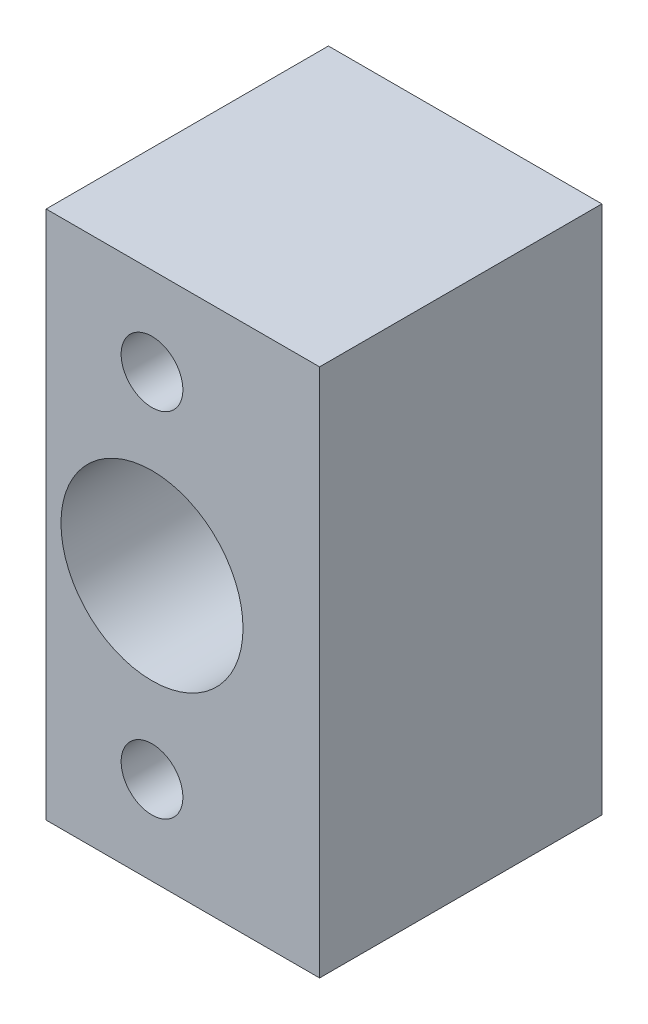
SolidWorks part; units mm, degrees
material "6061-T4 (SS)"
ref_plane "Front Plane" through (0, 0, 0) normal (0, 0, 1) x (1, 0, 0)
ref_plane "Top Plane" through (0, 0, 0) normal (0, 1, 0) x (1, 0, 0)
ref_plane "Right Plane" through (0, 0, 0) normal (1, 0, 0) x (0, 0, -1)
sketch "Sketch1" plane through (0, 0, 0) normal (0, 0, 1) x (1, 0, 0)
  line L5 (-6, 6) -> (0, 0) construction
  line L6 (0, 0) -> (6, 6) construction
  line L7 (9.5, 15) -> (-9.5, 15)
  line L8 (9.5, 15) -> (9.5, -15)
  line L9 (9.5, -15) -> (-9.5, -15)
  line L10 (-9.5, 15) -> (-9.5, -15)
  line L11 (9.5, 15) -> (-9.5, -15) construction
  line L12 (9.5, -15) -> (-9.5, 15) construction
  point P0 (0, 0)
  dimension "D1" = 19
  dimension "D4" = 30
extrude "Boss-Extrude1" add sketch "Sketch1" along normal blind 18
sketch "Sketch2" plane through (0, 0, 18) normal (0, 0, 1) x (1, 0, 0)
  circle A0 centre (0, 0) radius 5.1594
  dimension "D1" = 10.3187
extrude "Cut-Extrude1" cut sketch "Sketch2" against normal blind 11.5 contours A0
sketch "Sketch4" plane through (0, 0, 6.5) normal (0, 0, 1) x (1, 0, 0)
  circle A0 centre (0, 0) radius 4.8
  dimension "D1" = 9.6
extrude "Cut-Extrude3" cut sketch "Sketch4" against normal blind 0.5
sketch "Sketch5" plane through (0, 0, 6) normal (0, 0, 1) x (1, 0, 0)
  circle A0 centre (0, 0) radius 2.3813
  dimension "D1" = 4.7625
extrude "Cut-Extrude4" cut sketch "Sketch5" against normal blind 8 and the other way through all
sketch "Sketch6" plane through (0, 0, 0) normal (0, 0, 1) x (1, 0, 0)
  line L0 (-6, 15) -> (-6, -15)
  line L3 (9.5, 15) -> (-9.5, 15) construction
  line L4 (-9.5, -15) -> (9.5, -15) construction
  circle A0 centre (0, 0) radius 5.1594 construction
  point P6 (-6, 0)
  dimension "D1" = 6
extrude "Cut-Extrude6" cut sketch "Sketch6" against normal through all and the other way through all flip side to cut
sketch "Sketch11" plane through (0, 0, 0) normal (0, 0, -1) x (-1, 0, 0)
  line L1 (6, 15) -> (-9.5, 15)
  line L2 (6, 15) -> (6, -15)
  line L3 (6, -15) -> (-9.5, -15)
  line L4 (-9.5, 15) -> (-9.5, -15)
extrude "Boss-Extrude5" add sketch "Sketch11" along normal blind 5
sketch "Sketch12" plane through (0, 0, -5) normal (0, 0, -1) x (-1, 0, 0)
  circle A0 centre (0, 0) radius 4
  dimension "D1" = 8
extrude "Cut-Extrude8" cut sketch "Sketch12" against normal blind 7.9
sketch "Sketch13" plane through (0, 0, -5) normal (0, 0, -1) x (-1, 0, 0)
  line L2 (6, 15) -> (-9.5, 15) construction
  line L3 (0, 15) -> (0, -15) construction
  line L4 (-9.5, -15) -> (6, -15) construction
  circle A1 centre (0, -10) radius 1.75
  circle A2 centre (0, 10) radius 1.75
  point P0 (0, 5)
  point P4 (0, -5)
  point P6 (0, 0)
  dimension "D3" = 3.5
  dimension "D4" = 10
  dimension "D1" = 5
  dimension "D2" = 5
extrude "Cut-Extrude9" cut sketch "Sketch13" against normal through all
sketch "Sketch15" plane through (0, -15, 0) normal (0, -1, 0) x (1, 0, 0)
  line L1 (-6, -5) -> (9.5, -5) construction
  line L2 (-6, -5) -> (-6, 16) construction
  line L3 (-6, 16) -> (9.5, 16)
  line L4 (9.5, -5) -> (9.5, 16) construction
  line L5 (9.5, 18) -> (9.5, -5) construction
  line L6 (-6, 16) -> (9.5, 16)
  line L7 (-6, 16) -> (-6, 17) construction
  line L8 (-6, 17) -> (9.5, 17) construction
  line L9 (9.5, 16) -> (9.5, 17) construction
  line L10 (-6, -5) -> (9.5, -5)
  line L11 (-6, 18) -> (9.5, 18)
  line L12 (-6, 18) -> (-6, 16)
  line L13 (-6, 16) -> (9.5, 16)
  line L14 (9.5, 18) -> (9.5, 16)
  line L15 (-6, -5) -> (-6, 0)
  line L16 (-6, 0) -> (9.5, 0)
  line L17 (9.5, -5) -> (9.5, 0)
  line M5 (9.5, 18) -> (-6, 18)
  line M6 (-6, 18) -> (-6, -5)
  line M8 (9.5, -5) -> (9.5, 18)
  dimension "D1" = 21
  dimension "D2" = 1
  dimension "D3" = 5
extrude "Cut-Extrude11" cut sketch "Sketch15" against normal blind 41 contours L3 M6 M8 M5 | L15 L10 L17 L16 region at (1.75, -15, 17)
ref_axis "Axis1" through (-6, -15, 0) along (0.4148, 0.8029, 0.4282)
ref_plane "Plane2" through (-6, -15, 0) normal (0.4148, 0.8029, 0.4282) x (0.9099, -0.366, -0.1952)
sketch "Sketch17" plane through (-6, -15, 0) normal (0.4148, 0.8029, 0.4282) x (0.9099, -0.366, -0.1952)
  circle A0 centre (0, 0) radius 5
  dimension "D1" = 10
extrude "Cut-Extrude12" cut sketch "Sketch17" along normal blind 2
sketch "Sketch18" plane through (-5.1983, -10.0612, -5.366) normal (-0.4148, -0.8029, -0.4282) x (0.9088, -0.3427, -0.2379)
  point P0 (-0.3126, 7.052)
sketch "Sketch20" plane through (0, 0, 0) normal (0, 0, -1) x (-1, 0, 0)
  circle A0 centre (0, 10) radius 3.81
  circle A1 centre (0, -10) radius 3.81
  circle A3 centre (0, -10) radius 1.75 construction
  circle A4 centre (0, 10) radius 1.75 construction
  dimension "D1" = 7.62
extrude "Cut-Extrude13" cut sketch "Sketch20" against normal blind 4
